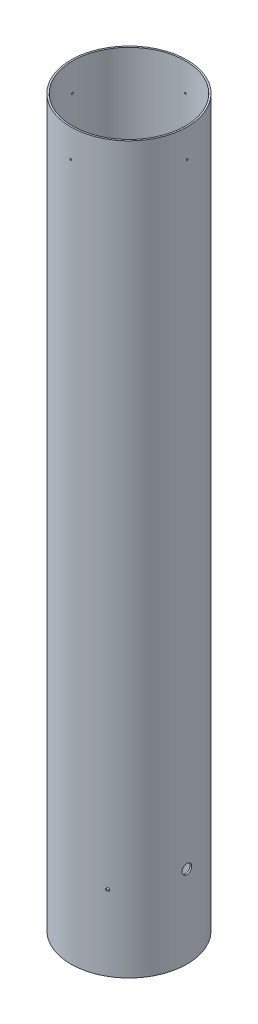
SolidWorks part; units mm, degrees
material "A-Glass Fiber"
ref_plane "Front Plane" through (0, 0, 0) normal (0, 0, 1) x (1, 0, 0)
ref_plane "Top Plane" through (0, 0, 0) normal (0, 1, 0) x (1, 0, 0)
ref_plane "Right Plane" through (0, 0, 0) normal (1, 0, 0) x (0, 0, -1)
sketch "Sketch1" plane through (0, 0, 0) normal (0, 1, 0) x (1, 0, 0)
  circle A0 centre (0, 0) radius 76.1746
  circle A1 centre (0, 0) radius 78.359
  dimension "D1" = 156.718
  dimension "D2" = 152.3492
extrude "Boss-Extrude1" add sketch "Sketch1" along normal blind 977.9
ref_axis "Axis1" through (0, 977.9, 0) along (0, -1, 0)
sketch "Sketch2" plane through (0, 0, 0) normal (1, 0, 0) x (0, 0, -1)
  line L0 (78.359, 977.9) -> (-78.359, 977.9) construction
  circle A0 centre (0, 939.8) radius 1.0922
  dimension "D1" = 2.1844
  dimension "D2" = 38.1
extrude "Cut-Extrude1" cut sketch "Sketch2" against normal through all
pattern_circular "CirPattern1" count 4 over 360 about axis through (0, 977.9, 0) along (0, 1, 0) of "Cut-Extrude1"
hole_wizard "1/2 Clearance Hole1" positions "Sketch3" profile "Sketch4" hole size "1/2" standard "ANSI Inch"
sketch "Sketch3" plane through (0, 0, 0) normal (1, 0, 0) x (0, 0, -1)
  point P0 (0, 111.125)
  dimension "D1" = 111.125
sketch "Sketch4" plane through (0, 111.125, 0) normal (0, 1, 0) x (0, 0, 1)
  line L0 (0, 0) -> (0, 92.8345)
  line L1 (0, 92.8345) -> (6.5481, 88.9)
  line L2 (6.5481, 88.9) -> (6.5481, 0)
  line L5 (6.5481, 0) -> (0, 0)
  line L10 (0, 92.8345) -> (-6.5481, 88.9) construction
  line L11 (0, -6.35) -> (0, 107.95) construction
  dimension "Hole Dia." = 13.0962
  dimension "Hole Depth" = 88.9
  dimension "Drill Angle" = 118
hole_wizard "Ø4.0 (4) Diameter Hole1" positions "Sketch5" profile "Sketch6" hole size "Ø4.0" standard "ANSI Metric"
sketch "Sketch5" plane through (0, 0, 0) normal (1, 0, 0) x (0, 0, -1)
  point P0 (0, 101.6)
  dimension "D1" = 101.6
sketch "Sketch6" plane through (0, 101.6, 0) normal (0, 1, 0) x (0, 0, -1)
  line L0 (0, 0) -> (0, 90.1017)
  line L1 (0, 90.1017) -> (2, 88.9)
  line L2 (2, 88.9) -> (2, 0)
  line L5 (2, 0) -> (0, 0)
  line L10 (0, 90.1017) -> (-2, 88.9) construction
  line L11 (0, -6.35) -> (0, 107.95) construction
  dimension "Hole Dia." = 4
  dimension "Hole Depth" = 88.9
  dimension "Drill Angle" = 118
pattern_circular "CirPattern2" count 3 over 360 about axis through (0, 0, 0) along (0, 1, 0) of "Ø4.0 (4) Diameter Hole1"
equation "\"Fwd_Tube_Length\" = 38.5in"
equation "\"D1@Boss-Extrude1\" = \"Fwd_Tube_Length\""
equation "\"BKHD_Screw_Diam\"= 3.5mm"
equation "\"Fwd_BKHD_From_Top\" = 18in"
equation "\"Bodytube_OD\" = 6.17in"
equation "\"Bodytube_ID\" = 5.998in"
equation "\"D2@Sketch1\"=\"Bodytube_ID\""
equation "\"D1@Sketch1\"=\"Bodytube_OD\""
equation "\"Shear_Screw_Diameter\" = 0.086in"
equation "\"Shear_Screw_Coupler_Location\" = 4.5in"
equation "\"Motor_OD\" = 4in"
equation "\"Mid_Tube_Length\"= 1in"
equation "\"Mid_Coupler_Length\" = 13in"
equation "\"Aft_Section_Length\"= 36in"
equation "\"AB_Coupler_OD_Length\"= 1in"
equation "\"AB_Coupling_Section_Length\"= 0.375in"
equation "\"AB_Coupler_Length\"= \"AB_Coupler_OD_Length\" + \"AB_Coupling_Section_Length\" * 2"
equation "\"Cutout_Angle\" = 80"
equation "\"AB_Paddle_Height\" = 0.375in"
equation "\"AB_Coupler_Num_Screws\"= 4"
equation "\"AB_BKHD_Thickness\" = 0.375in"
equation "\"AB_Mount_From_Bottom\" = 23.175in"
equation "\"Num_Cutouts\" = 3"
equation "\"AB_Coupler_OD\"= 6.17in"
equation "\"AB_Coupler_ID\"= 5.75in"
equation "\"AB_Coupler_Surface_Diameter\"= 5.998in"
equation "\"AB_Coupling_Screw_Diameter\"= 0.15748in"
equation "\"AB_Central_Bushing_Length\" = .4724in"
equation "\"Lead_Screw_Dist\" = 3.4in"
equation "\"Lead_Screw_Diam\" = 0.386in"
equation "\"Lead_Screw_Length\" = (\"Mid_Coupler_Length\" + 2*0.375in + 2*.75in)"
equation "\"Paddle_Pin_Offset\" = .25in"
equation "\"Paddle_Pin_Radius\" = 2.25in"
equation "\"SS_Paddle_Pin_Radius\" = 2.25*0.66in"
equation "\"Paddle_Gear_OD\" = 3.2in"
equation "\"Drive_Gear_OD\" = 1.7in"
equation "\"Fin_Thickness\"= .118in"
equation "\"Guiderail_Cutout_Diameter\"= 1.5in"
equation "\"DB9_Hole_Dist\" = 25mm"
equation "\"DB9_Relief_Width\" = 0.47in"
equation "\"DB9_Relief_Hole_Offset\" = 0.09in"
equation "\"Airbrakes_Wire_Hole_Dia\" = .25in"
equation "\"Airbrakes_Wire_Hole_Dist\" = 1.1in"
equation "\"Servo_Gear_Offset\" = 0.5in"
equation "\"D1@Sketch2\"=\"Shear_Screw_Diameter\""
equation "\"FWD_Shear_Screw_Dist\" = 1.5in"
equation "\"D2@Sketch2\"=\"FWD_Shear_Screw_Dist\""
